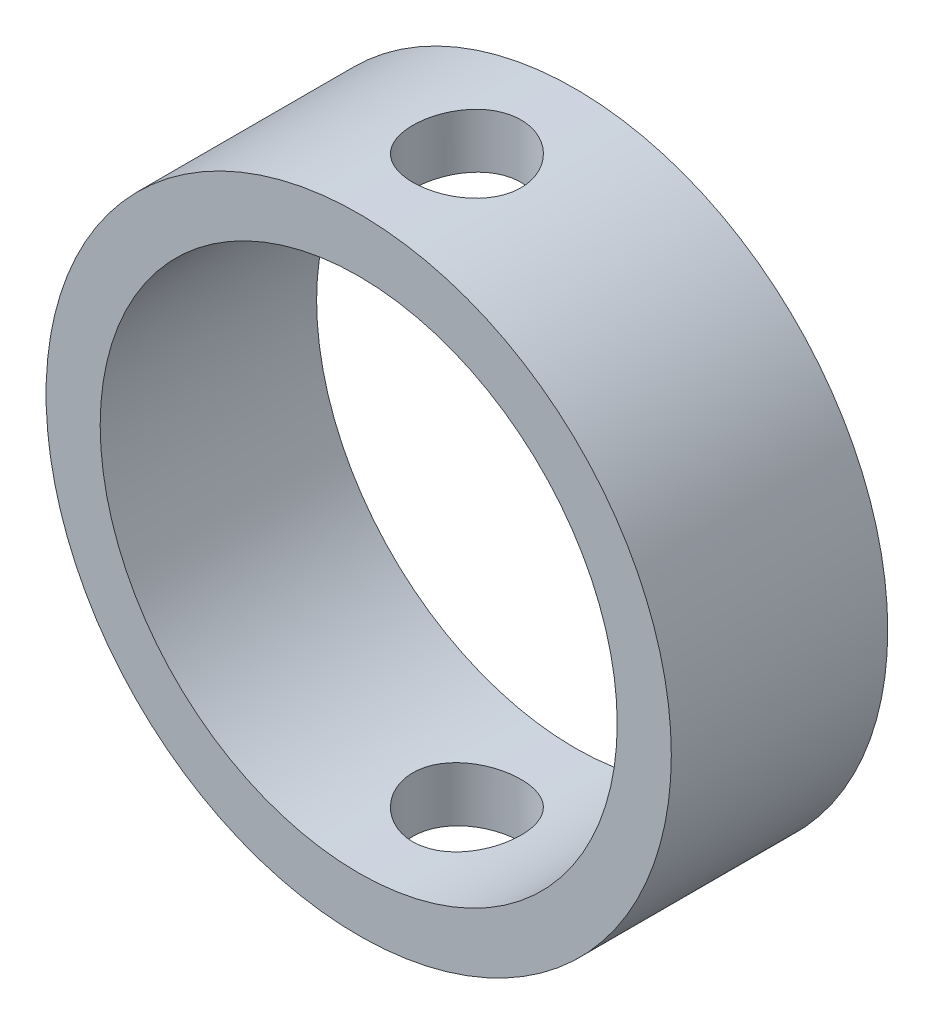
SolidWorks part; units mm, degrees
ref_plane "Front" through (0, 0, 0) normal (0, 0, 1) x (1, 0, 0)
ref_plane "Top" through (0, 0, 0) normal (0, 1, 0) x (1, 0, 0)
ref_plane "Right" through (0, 0, 0) normal (1, 0, 0) x (0, 0, -1)
sketch "Sketch1" plane through (0, 0, 0) normal (0, 0, 1) x (1, 0, 0)
  circle A0 centre (0, 0) radius 36.6889
  circle A1 centre (0, 0) radius 30.3389
  dimension "D1" = 6.35
  dimension "D2" = 73.3778
extrude "Ring" add sketch "Sketch1" along normal blind 12.7 and the other way blind 12.7
sketch "Sketch5" plane through (0, 0, 0) normal (0, 1, 0) x (1, 0, 0)
  circle A0 centre (0, 0) radius 6.35
extrude "Shaft Hole" cut sketch "Sketch5" against normal through all and the other way through all
